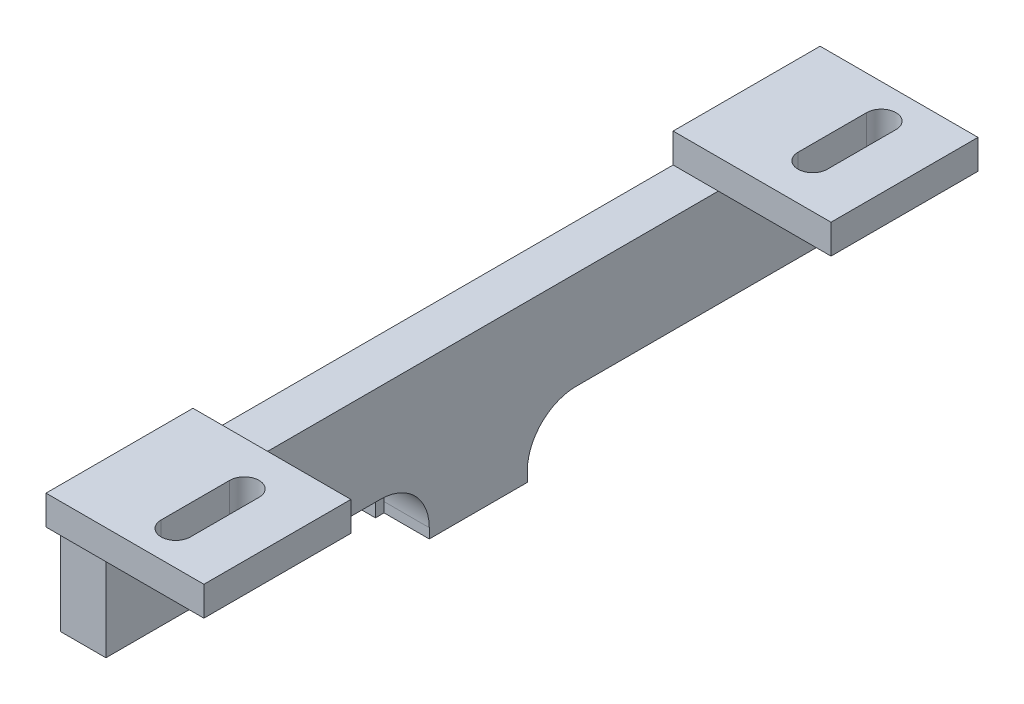
SolidWorks part; units mm, degrees
ref_plane "Front Plane" through (0, 0, 0) normal (0, 0, 1) x (1, 0, 0)
ref_plane "Top Plane" through (0, 0, 0) normal (0, 1, 0) x (1, 0, 0)
ref_plane "Right Plane" through (0, 0, 0) normal (1, 0, 0) x (0, 0, -1)
sketch "Sketch1" plane through (0, 0, 0) normal (0, 1, 0) x (1, 0, 0)
  line L0 (0, 8.5) -> (0, -8.5) construction
  line L1 (-3, -11.3279) -> (3, -11.3279)
  line L2 (-3, -11.3279) -> (-3, 11.3279)
  line L3 (-3, 11.3279) -> (3, 11.3279)
  line L4 (3, -11.3279) -> (3, -5)
  line L5 (-3, -11.3279) -> (3, 11.3279) construction
  line L6 (-3, 11.3279) -> (3, -11.3279) construction
  line L7 (3, -5) -> (7.6154, -5)
  line L8 (7.6154, -5) -> (7.6154, 5)
  line L9 (7.6154, 5) -> (3, 5)
  line L10 (3, 5) -> (3, 11.3279)
  circle A0 centre (0, 8.5) radius 1.5
  circle A1 centre (0, -8.5) radius 1.5
  point P0 (0, 0)
  point P10 (0, 0)
  point P13 (7.6154, 0)
  point P16 (-3, 0)
  dimension "D1" = 3
  dimension "D2" = 17
  dimension "D3" = 6
  dimension "D4" = 10
extrude "Boss-Extrude1" add sketch "Sketch1" along normal blind 3
sketch "Sketch3" plane through (0, 3, 0) normal (0, 1, 0) x (1, 0, 0)
  line L0 (7.6154, 5) -> (3, 5) construction
  line L1 (7.6154, 5) -> (3, 5)
  line L2 (7.6154, 5) -> (7.6154, -5)
  line L3 (7.6154, -5) -> (3, -5)
  line L4 (3, 5) -> (3, -5)
  line L5 (7.6154, -5) -> (7.6154, 5) construction
  line L6 (3, -5) -> (7.6154, -5) construction
extrude "Boss-Extrude2" add sketch "Sketch3" along normal blind 12.9998
fillet "Fillet7" radius 1 2 edges at (3, 1.5, -11.3279) (3, 1.5, 11.3279)
sketch "Sketch7" plane through (0, 0, 0) normal (0, -1, 0) x (1, 0, 0)
  line L0 (-3.6553, -6.3921) -> (-3.7819, 6.4785)
  arc A0 (-3.6553, -6.3921) -> (-3.7819, 6.4785) centre (-8.1114, 0) ccw
extrude "Cut-Extrude4" cut sketch "Sketch7" against normal blind 10
fillet "Fillet8" radius 4 1 edges at (3, 3, 0)
sketch "Sketch8" plane through (7.6154, 0, 0) normal (1, 0, 0) x (0, 0, -1)
  line L0 (-5, 15.9998) -> (5, 15.9998) construction
  line L1 (-38, 5.9998) -> (38, 5.9998)
  line L2 (-38, 5.9998) -> (-38, 15.9998)
  line L3 (-38, 15.9998) -> (38, 15.9998)
  line L4 (38, 5.9998) -> (38, 15.9998)
  line L7 (-5, 0) -> (5, 0) construction
  point P0 (0, 10.9824)
  point P9 (0, 0)
  point P10 (0, 5.9998)
  dimension "D1" = 10
  dimension "D2" = 76
extrude "Boss-Extrude3" add sketch "Sketch8" against normal up to surface (4.6154 mm away) up to face at (3, 9.9902, -0.0004)
sketch "Sketch9" plane through (0, 15.9998, 0) normal (0, 1, 0) x (1, 0, 0)
  line L0 (7.6154, -38) -> (7.6154, 38) construction
  line L1 (3, 38) -> (17.6154, 38)
  line L2 (3, 38) -> (3, 26)
  line L3 (3, 26) -> (17.6154, 26)
  line L4 (17.6154, 38) -> (17.6154, 26)
  line L5 (3, -38) -> (17.6154, -38)
  line L6 (3, -38) -> (3, -26)
  line L7 (3, -26) -> (17.6154, -26)
  line L8 (17.6154, -38) -> (17.6154, -26)
  line L9 (12.7451, 32.5) -> (12.7451, -32.5) construction
  circle A0 centre (12.7451, 32.5) radius 1.5
  circle A1 centre (12.7451, -32.5) radius 1.5
  point P16 (7.6154, 0)
  point P17 (12.7451, 0)
  dimension "D2" = 3
  dimension "D1" = 10
  dimension "D3" = 65
  dimension "D4" = 12
extrude "Boss-Extrude4" add sketch "Sketch9" along normal blind 3
fillet "Fillet9" radius 5 1 edges at (5.3077, 5.9998, 5)
fillet "Fillet10" radius 5 1 edges at (5.3077, 5.9998, -5)
sketch "Sketch10" plane through (0, 3, 0) normal (0, 1, 0) x (1, 0, 0)
  line L0 (3.5564, 5.88) -> (3.5564, -5.88) construction
  line L1 (3.5564, 15.865) -> (-6.2169, 15.865)
  line L2 (3.5564, 15.865) -> (3.5564, 5.88)
  line L3 (3.5564, 5.88) -> (-6.2169, 5.88)
  line L4 (-6.2169, 15.865) -> (-6.2169, 5.88)
  line L5 (-9.1574, -13.6403) -> (3.5564, -13.6403)
  line L6 (-9.1574, -13.6403) -> (-9.1574, -5.88)
  line L7 (-9.1574, -5.88) -> (3.5564, -5.88)
  line L8 (3.5564, -13.6403) -> (3.5564, -5.88)
  line L9 (7.6154, -26) -> (7.6154, 26) construction
  point P10 (7.6154, 0)
  point P11 (3.5564, 0)
  dimension "D1" = 11.76
extrude "Cut-Extrude6" cut sketch "Sketch10" against normal blind 10
sketch "Sketch11" plane through (0, 18.9998, 0) normal (0, 1, 0) x (1, 0, 0)
  line L0 (12.7451, 36) -> (12.7451, 29) construction
  line L1 (14.2451, 36) -> (14.2451, 29)
  line L2 (11.2451, 36) -> (11.2451, 29)
  line L3 (12.7451, -29) -> (12.7451, -36) construction
  line L4 (14.2451, -29) -> (14.2451, -36)
  line L5 (11.2451, -29) -> (11.2451, -36)
  arc A0 (14.2451, 36) -> (11.2451, 36) centre (12.7451, 36) ccw
  arc A1 (11.2451, 29) -> (14.2451, 29) centre (12.7451, 29) ccw
  circle A2 centre (12.7451, 32.5) radius 1.5 construction
  arc A3 (14.2451, -29) -> (11.2451, -29) centre (12.7451, -29) ccw
  arc A4 (11.2451, -36) -> (14.2451, -36) centre (12.7451, -36) ccw
  circle A5 centre (12.7451, -32.5) radius 1.5 construction
  point P2 (12.7451, 32.5)
  point P11 (12.7451, -32.5)
  dimension "D1" = 1.5
  dimension "D3" = 1.5
  dimension "D2" = 7
  dimension "D4" = 7
extrude "Cut-Extrude7" cut sketch "Sketch11" against normal through all
sketch "Sketch13" plane through (0, 18.9998, 0) normal (0, 1, 0) x (1, 0, 0)
  line L0 (3, -38) -> (3, -39.5)
  line L1 (3, -38) -> (17.6154, -38) construction
  line L2 (3, -26) -> (3, -38) construction
  line L3 (3, -39.5) -> (19.1154, -39.5)
  line L4 (19.1154, -39.5) -> (19.1154, -24.5)
  line L5 (19.1154, -24.5) -> (3, -24.5)
  line L6 (3, -24.5) -> (3, -26)
  line L7 (3, -26) -> (17.6154, -26)
  line L8 (17.6154, -26) -> (17.6154, -38)
  line L9 (17.6154, -38) -> (3, -38)
  line L10 (3, 26) -> (3, 24.5)
  line L11 (3, 24.5) -> (19.1154, 24.5)
  line L12 (19.1154, 24.5) -> (19.1154, 39.5)
  line L13 (19.1154, 39.5) -> (3, 39.5)
  line L14 (3, 39.5) -> (3, 38)
  line L15 (3, 38) -> (17.6154, 38)
  line L16 (17.6154, 38) -> (3, 38) construction
  line L17 (17.6154, 38) -> (17.6154, 26)
  line L18 (17.6154, 26) -> (3, 26)
  line L19 (17.6154, 26) -> (17.6154, 38) construction
  dimension "D1" = 1.5
  dimension "D2" = 1.5
  dimension "D3" = 1.5
  dimension "D4" = 1.5
  dimension "D5" = 1.5
  dimension "D6" = 1.5
extrude "Boss-Extrude5" add sketch "Sketch13" against normal up to surface (3 mm away) up to face at (12.7451, 15.9998, 32.5)
